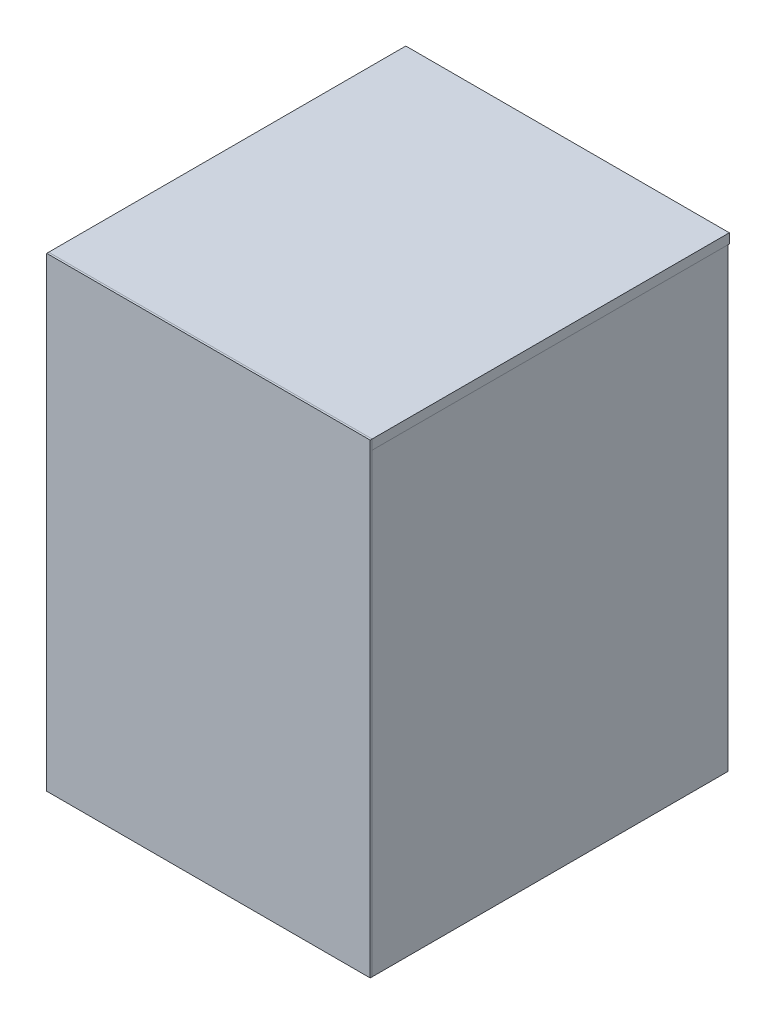
SolidWorks part; units mm, degrees
ref_plane "Front" through (0, 0, 0) normal (0, 0, 1) x (1, 0, 0)
ref_plane "Top" through (0, 0, 0) normal (0, 1, 0) x (1, 0, 0)
ref_plane "Right" through (0, 0, 0) normal (1, 0, 0) x (0, 0, -1)
sketch "Sketch1" plane through (0, 0, 0) normal (0, 0, 1) x (1, 0, 0)
  line L0 (0, 0) -> (0, 690) construction
  line L1 (-250, 690) -> (-235, 690)
  line L2 (-250, 690) -> (-250, -15)
  line L3 (-250, -15) -> (-235, -15)
  line L4 (-235, 690) -> (-235, -15)
  line L5 (235, 690) -> (235, -15)
  line L6 (250, -15) -> (235, -15)
  line L7 (250, 690) -> (250, -15)
  line L8 (250, 690) -> (235, 690)
  dimension "D1" = 15
  dimension "D2" = 470
  dimension "D3" = 15
  dimension "D4" = 690
extrude "Boss-Extrude1" add sketch "Sketch1" along normal blind 550
sketch "Sketch2" plane through (0, 0, 0) normal (0, 0, 1) x (1, 0, 0)
  line L0 (235, 690) -> (235, -15) construction
  line L1 (-235, -15) -> (235, -15)
  line L2 (-235, -15) -> (-235, 0)
  line L3 (-235, 0) -> (235, 0)
  line L4 (235, -15) -> (235, 0)
  line L5 (-250, -15) -> (-235, -15) construction
extrude "Boss-Extrude2" add sketch "Sketch2" along normal offset from surface (515 mm away) 15 from offset 20 separate body up to face at (-242.5, 337.5, 550)
sketch "Sketch3" plane through (0, 0, 0) normal (0, 0, 1) x (1, 0, 0)
  line L0 (250, -15) -> (250, 690) construction
  line L1 (-250, 690) -> (250, 690)
  line L2 (-250, 690) -> (-250, 705)
  line L3 (-250, 705) -> (250, 705)
  line L4 (250, 690) -> (250, 705)
  line L5 (-250, -15) -> (-235, -15) construction
extrude "Boss-Extrude3" add sketch "Sketch3" along normal up to surface (550 mm away) from offset 2 separate body up to face at (-242.5, 337.5, 550) offset against normal yes
sketch "Sketch4" plane through (0, 0, 20) normal (0, 0, -1) x (-1, 0, 0)
  line L0 (-235, 690) -> (-235, -15) construction
  line L1 (-235, 600) -> (235, 600)
  line L2 (-235, 600) -> (-235, 585)
  line L3 (-235, 585) -> (235, 585)
  line L4 (235, 600) -> (235, 585)
  line L5 (235, -15) -> (235, 690) construction
  line L6 (235, 0) -> (235, -15) construction
  line L7 (250, 690) -> (-250, 690) construction
  dimension "D1" = 105
extrude "Boss-Extrude4" add sketch "Sketch4" against normal blind 50
sketch "Sketch5" plane through (0, 0, 0) normal (1, 0, 0) x (0, 0, -1)
  line L0 (-550, 690) -> (0, 690) construction
  line L1 (-550, 690) -> (-535, 690)
  line L2 (-550, 690) -> (-550, 640)
  line L3 (-550, 640) -> (-535, 640)
  line L4 (-535, 690) -> (-535, 640)
  line L5 (-70, 585) -> (-85, 585)
  line L6 (-70, 585) -> (-70, 690)
  line L7 (-70, 690) -> (-85, 690)
  line L8 (-85, 585) -> (-85, 690)
  line L9 (-20, 600) -> (-20, 585) construction
  dimension "D1" = 50
extrude "Boss-Extrude5" add sketch "Sketch5" along normal up to next and the other way up to next separate body
sketch "Sketch7" plane through (0, 0, 550) normal (0, 0, 1) x (1, 0, 0)
  line L1 (-250, 705) -> (250, 705)
  line L2 (-250, 705) -> (-250, -15)
  line L3 (-250, -15) -> (250, -15)
  line L4 (250, 705) -> (250, -15)
extrude "Boss-Extrude6" add sketch "Sketch7" along normal blind 3 separate body
sketch "Sketch10" plane through (0, 0, 70) normal (0, 0, -1) x (-1, 0, 0)
  line L0 (-40, 645) -> (40, 645) construction
  line L1 (-40, 682.5) -> (40, 682.5)
  line L2 (-40, 607.5) -> (40, 607.5)
  line L3 (-235, 690) -> (-235, 600) construction
  arc A0 (-40, 682.5) -> (-40, 607.5) centre (-40, 645) ccw
  arc A1 (40, 607.5) -> (40, 682.5) centre (40, 645) ccw
  point P2 (0, 645)
  point P7 (-235, 645)
  point P13 (0, 607.5)
  dimension "D1" = 80
  dimension "D2" = 75
extrude "Cut-Extrude2" cut sketch "Sketch10" against normal up to next (15 mm away)
sketch "Sketch8" plane through (0, 0, 0) normal (0, 1, 0) x (1, 0, 0)
  line L2 (235, -30) -> (235, -20)
  line L3 (235, -535) -> (235, -20) construction
  line L4 (235, -20) -> (220, -20)
  line L5 (235, -20) -> (-235, -20) construction
  dimension "D1" = 15
  dimension "D2" = 10
extrude "Alu-profiles" add sketch "Sketch8" along normal up to surface (585 mm away) separate body thin up to face at (0, 585, 45) thin type one direction reverse wall 2
mirror "Mirror2" about plane through (0, 0, 0) normal (1, 0, 0) of bodies 109
sketch "Sketch9" plane through (0, 0, 20) normal (0, 0, -1) x (-1, 0, 0)
  line L0 (0, 705) -> (0, 292.5) construction
  line L2 (0, 292.5) -> (-220, 292.5) construction
  line L5 (-250, 705) -> (250, 705) construction
  line L6 (-220, 585) -> (-220, 0) construction
  circle A0 centre (-225, 517.5) radius 2.5
  circle A1 centre (-225, 67.5) radius 2.5
  circle A2 centre (225, 67.5) radius 2.5
  circle A3 centre (225, 517.5) radius 2.5
  dimension "D1" = 5
  dimension "D2" = 450
  dimension "D3" = 450
extrude "Cut-Extrude1" cut sketch "Sketch9" against normal up to next (2 mm away)
sketch "Sketch11" plane through (0, 690, 0) normal (0, -1, 0) x (1, 0, 0)
  line L0 (235, 550) -> (235, 0) construction
  line L1 (-235, 535) -> (235, 535)
  line L2 (-235, 535) -> (-235, 85)
  line L3 (-235, 85) -> (235, 85)
  line L4 (235, 535) -> (235, 85)
  line L5 (-235, 85) -> (235, 85) construction
  line L6 (235, 85) -> (235, 70) construction
split line "Split Line1"
